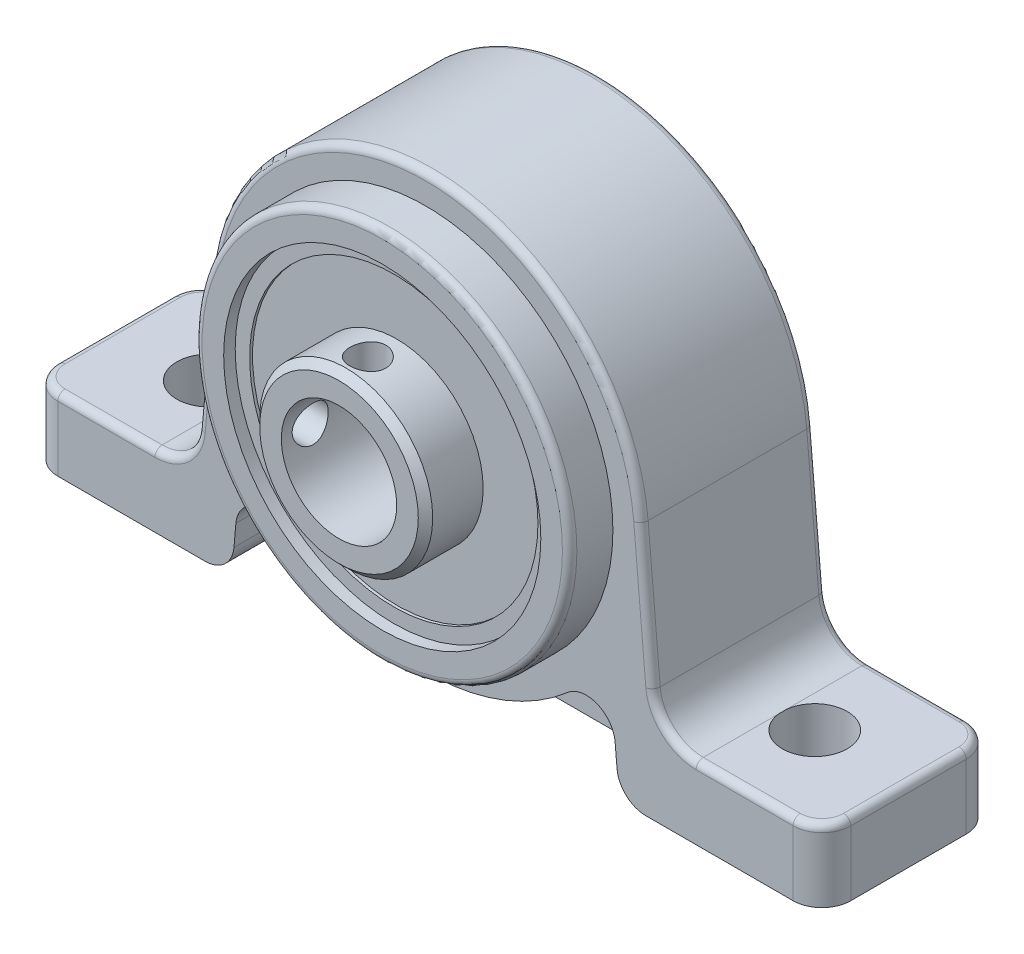
SolidWorks part; units mm, degrees
ref_plane "Front Plane" through (0, 0, 0) normal (0, 0, 1) x (1, 0, 0)
ref_plane "Top Plane" through (0, 0, 0) normal (0, 1, 0) x (1, 0, 0)
ref_plane "Right Plane" through (0, 0, 0) normal (1, 0, 0) x (0, 0, -1)
sketch "Sketch1" plane through (0, 0, 0) normal (0, 0, 1) x (1, 0, 0)
  line L0 (0, 0) -> (-11670.9506, 0) construction
  line L1 (0, 0) -> (0, 11670.9506) construction
  line L2 (-27.5, 0) -> (-27.5, 5)
  line L3 (-27.5, 5) -> (-18.7687, 5)
  line L4 (-27.5, 0) -> (-15.2783, 0)
  line L5 (-13.2859, 1.8257) -> (-13.1525, 3.3505)
  line L6 (-15.7801, 7.7385) -> (-14.9429, 17.3073)
  line L7 (27.5, -4.905) -> (-27.5, -4.905) construction
  line L8 (21, -4.905) -> (21, -1.8884) construction
  line L9 (-21, -4.905) -> (-21, -1.8884) construction
  line L10 (0, 0) -> (11670.9506, 0) construction
  line L11 (15.7801, 7.7385) -> (14.9429, 17.3073)
  line L12 (13.2859, 1.8257) -> (13.1525, 3.3505)
  line L13 (27.5, 0) -> (15.2783, 0)
  line L14 (27.5, 5) -> (18.7687, 5)
  line L15 (27.5, 0) -> (27.5, 5)
  circle A0 centre (0, 16) radius 4
  arc A1 (-9.8472, 4.6848) -> (9.8472, 4.6848) centre (0, 16) ccw
  circle A2 centre (0, 16) radius 13
  arc A3 (-15.7801, 7.7385) -> (-18.7687, 5) centre (-18.7687, 8) cw
  arc A4 (-13.2859, 1.8257) -> (-15.2783, 0) centre (-15.2783, 2) cw
  arc A5 (-9.8472, 4.6848) -> (-13.1525, 3.3505) centre (-11.1601, 3.1761) ccw
  circle A6 centre (0, 16) radius 15 construction
  circle A7 centre (0, 16) radius 6
  circle A8 centre (0, 16) radius 11
  circle A9 centre (0, 16) radius 10
  arc A10 (9.8472, 4.6848) -> (13.1525, 3.3505) centre (11.1601, 3.1761) cw
  arc A11 (13.2859, 1.8257) -> (15.2783, 0) centre (15.2783, 2) ccw
  arc A12 (15.7801, 7.7385) -> (18.7687, 5) centre (18.7687, 8) ccw
  arc A13 (14.9429, 17.3073) -> (-14.9429, 17.3073) centre (0, 16) ccw
  point P18 (0, -4.905)
  point P33 (-13.4457, 0)
  point P34 (14.3446, 20.3856)
  point P57 (13.4457, 0)
  dimension "D1" = 8
  dimension "D2" = 16
  dimension "D3" = 30
  dimension "D10" = 3
  dimension "D11" = 2
  dimension "D12" = 2
  dimension "D4" = 55
  dimension "D6" = 5
  dimension "D7" = 3
  dimension "D9" = 85
  dimension "D8" = 2
  dimension "D13" = 2
  dimension "D14" = 2
  dimension "D15" = 1
extrude "Boss-Extrude1" add sketch "Sketch1" along normal blind 12 contours L11 A13 L6 A3 L3 L2 L4 A4 L5 A5 A1 A10 L12 A11 L13 L15 L14 A12 A2 region at (-26.8687, 2.5, 0)
extrude "Boss-Extrude2" add sketch "Sketch1<3>" along normal blind 12 from offset 3 contours A2 A8 region at (-12.6323, 16, 0)
sketch "Sketch1<3>" plane through (0, 0, 0) normal (0, 0, 1) x (1, 0, 0) same geometry as "Sketch1"
extrude "Boss-Extrude3" add sketch "Sketch1<4>" along normal blind 11 from offset 3.2 contours A8 A9 region at (-10.6889, 16, 0)
sketch "Sketch1<4>" plane through (0, 0, 0) normal (0, 0, 1) x (1, 0, 0) same geometry as "Sketch1"
extrude "Boss-Extrude4" add sketch "Sketch1<6>" along normal blind 10.5 from offset 3.5 contours A9 A7 region at (-9.7172, 16, 0)
sketch "Sketch1<6>" plane through (0, 0, 0) normal (0, 0, 1) x (1, 0, 0) same geometry as "Sketch1"
extrude "Boss-Extrude5" add sketch "Sketch1<7>" along normal blind 15 from offset 3 contours A7 A0 region at (-5.8303, 16, 0)
sketch "Sketch1<7>" plane through (0, 0, 0) normal (0, 0, 1) x (1, 0, 0) same geometry as "Sketch1"
ref_plane "Plane1" through (0, 0, 6) normal (0, 0, 1) x (1, 0, 0)
sketch "Sketch2" plane through (0, 0, 6) normal (0, 0, 1) x (1, 0, 0)
  line L0 (15.2783, 0) -> (-15.2783, 0)
  line L1 (-15.2783, 0) -> (-15.2783, 5.5)
  line L2 (-15.2783, 5.5) -> (15.2783, 5.5)
  line L3 (15.2783, 5.5) -> (15.2783, 0)
  dimension "D1" = 30.5566
  dimension "D2" = 5.5
extrude "Boss-Extrude6" add sketch "Sketch2" along normal mid plane 4
sketch "Sketch3" plane through (0, 0, 0) normal (1, 0, 0) x (0, 0, -1)
  line L0 (-18, 16) -> (49982, 16) construction
  line L1 (-18, 22) -> (-18, 10) construction
  line L2 (-16, 22) -> (-16, -49978) construction
  line L3 (-14, 22) -> (-18, 22) construction
  circle A0 centre (-16, 16) radius 1.25
  point P4 (-18, 16)
  point P9 (-16, 22)
  dimension "D1" = 2.5
extrude "Cut-Extrude1" cut sketch "Sketch3" against normal up to next
pattern_circular "CirPattern1" count 2 over 90 about axis through (0, 16, 18) along (0, 0, -1) of "Cut-Extrude1"
fillet "Fillet1" radius 2 4 edges at (-27.5, 2.5, 0) (-27.5, 2.5, 12) (27.5, 2.5, 0) (27.5, 2.5, 12)
fillet "Fillet2" radius 0.5 21 edges at (15.3615, 12.5229, 12) (16.7419, 5.7882, 12) (22.1343, 5, 12) (26.9142, 5, 11.4142) (27.5, 5, 6) (26.9142, 5, 0.5858) (22.1343, 5, 0) (16.7419, 5.7882, 0) (15.3615, 12.5229, 0) (0, 31, 0) (-15.3615, 12.5229, 0) (-16.7419, 5.7882, 0) (-22.1343, 5, 0) (-26.9142, 5, 0.5858) (-27.5, 5, 6) (-26.9142, 5, 11.4142) (-22.1343, 5, 12) (-16.7419, 5.7882, 12) (-15.3615, 12.5229, 12) (0, 31, 12) (13, 16, 15)
fillet "Fillet3" radius 1 1 edges at (13, 16, 0)
chamfer "Chamfer1" distance 0.5 angle 45 1 edges at (6, 16, 18)
sketch "Sketch4" plane through (0, 5, 0) normal (0, 1, 0) x (1, 0, 0)
  line L0 (27.5, -6) -> (-27.5, -6) construction
  line L1 (27.5, -2) -> (27.5, -10) construction
  line L2 (-27.5, -10) -> (-27.5, -2) construction
  line L3 (-27.5, -6) -> (0, 0) construction
  line L4 (0, 0) -> (0, -17.5) construction
  line L5 (6, -17.5) -> (-6, -17.5) construction
  circle A0 centre (21, -6) radius 2.25
  circle A1 centre (-21, -6) radius 2.25
  dimension "D1" = 4.5
  dimension "D2" = 42
extrude "Cut-Extrude2" cut sketch "Sketch4" against normal through all
